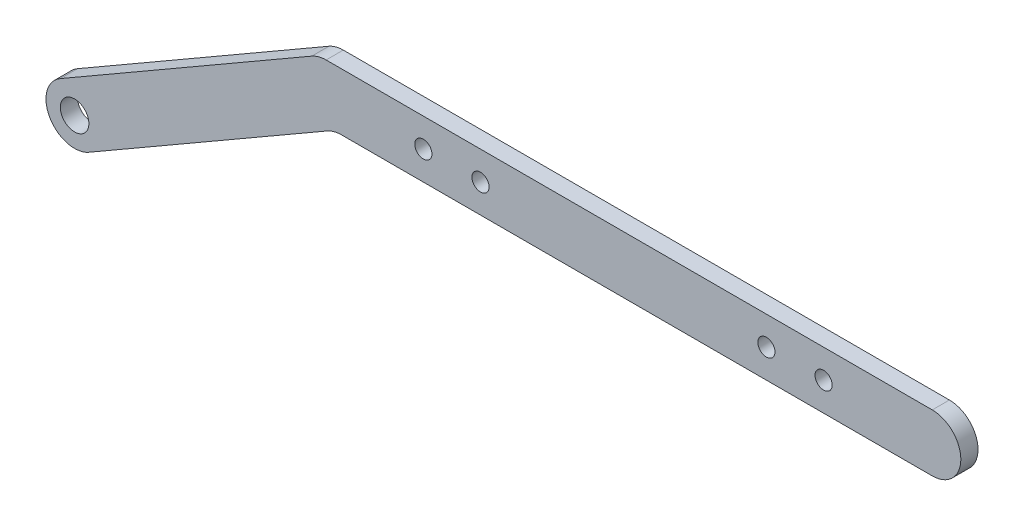
SolidWorks part; units mm, degrees
ref_plane "前视基准面" through (0, 0, 0) normal (0, 0, 1) x (1, 0, 0)
ref_plane "上视基准面" through (0, 0, 0) normal (0, 1, 0) x (1, 0, 0)
ref_plane "右视基准面" through (0, 0, 0) normal (1, 0, 0) x (0, 0, -1)
sketch "草图1" plane through (0, 0, 0) normal (0, 0, 1) x (1, 0, 0)
  line L0 (-52.2989, 0) -> (47.7011, 0) construction
  line L1 (-58.3058, 5) -> (47.7011, 5)
  line L2 (-55.6263, -5) -> (47.7011, -5)
  line L3 (-58.1263, -5.6699) -> (-99.7989, -29.7295)
  line L4 (-60.8058, 4.3301) -> (-104.7989, -21.0693)
  arc A0 (-99.7989, -29.7295) -> (-104.7989, -21.0693) centre (-102.2989, -25.3994) cw
  arc A1 (47.7011, -5) -> (47.7011, 5) centre (47.7011, 0) ccw
  arc A2 (-55.6263, -5) -> (-58.1263, -5.6699) centre (-55.6263, -10) ccw
  arc A3 (-58.3058, 5) -> (-60.8058, 4.3301) centre (-58.3058, 0) ccw
  circle A4 centre (-102.2989, -25.3994) radius 2.5
  point P3 (-2.2989, 0)
  dimension "D2" = 5
  dimension "D4" = 5
  dimension "D5" = 5
  dimension "D6" = 5
  dimension "D1" = 100
  dimension "D3" = 150
  dimension "D7" = 50
extrude "凸台-拉伸1" add sketch "草图1" along normal blind 3 contours L4 A0 L3 A2 L2 A1 L1 A3
sketch "草图2" plane through (0, 0, 3) normal (0, 0, 1) x (1, 0, 0)
  circle A0 centre (-102.2989, -25.3994) radius 2.5
  arc A1 (-104.7989, -21.0693) -> (-99.7989, -29.7295) centre (-102.2989, -25.3994) ccw construction
  dimension "D1" = 5
extrude "切除-拉伸1" cut sketch "草图2" against normal blind 3
sketch "草图3" plane through (0, 0, 3) normal (0, 0, 1) x (1, 0, 0)
  line L0 (-58.3058, 5) -> (47.7011, 5) construction
  circle A0 centre (-31.3036, 0) radius 1.5
  circle A1 centre (-41.3036, 0) radius 1.5
  dimension "D1" = 3
  dimension "D2" = 3
  dimension "D3" = 10
  dimension "D4" = 5
extrude "切除-拉伸2" cut sketch "草图3" against normal blind 3
sketch "草图4" plane through (0, 0, 0) normal (0, 0, -1) x (-1, 0, 0)
  circle A0 centre (-18.6964, 0) radius 1.5 construction
  circle A1 centre (-28.6964, 0) radius 1.5 construction
  circle A2 centre (-18.6964, 0) radius 1.5
  circle A3 centre (-28.6964, 0) radius 1.5
extrude "切除-拉伸3" cut sketch "草图4" against normal through all
